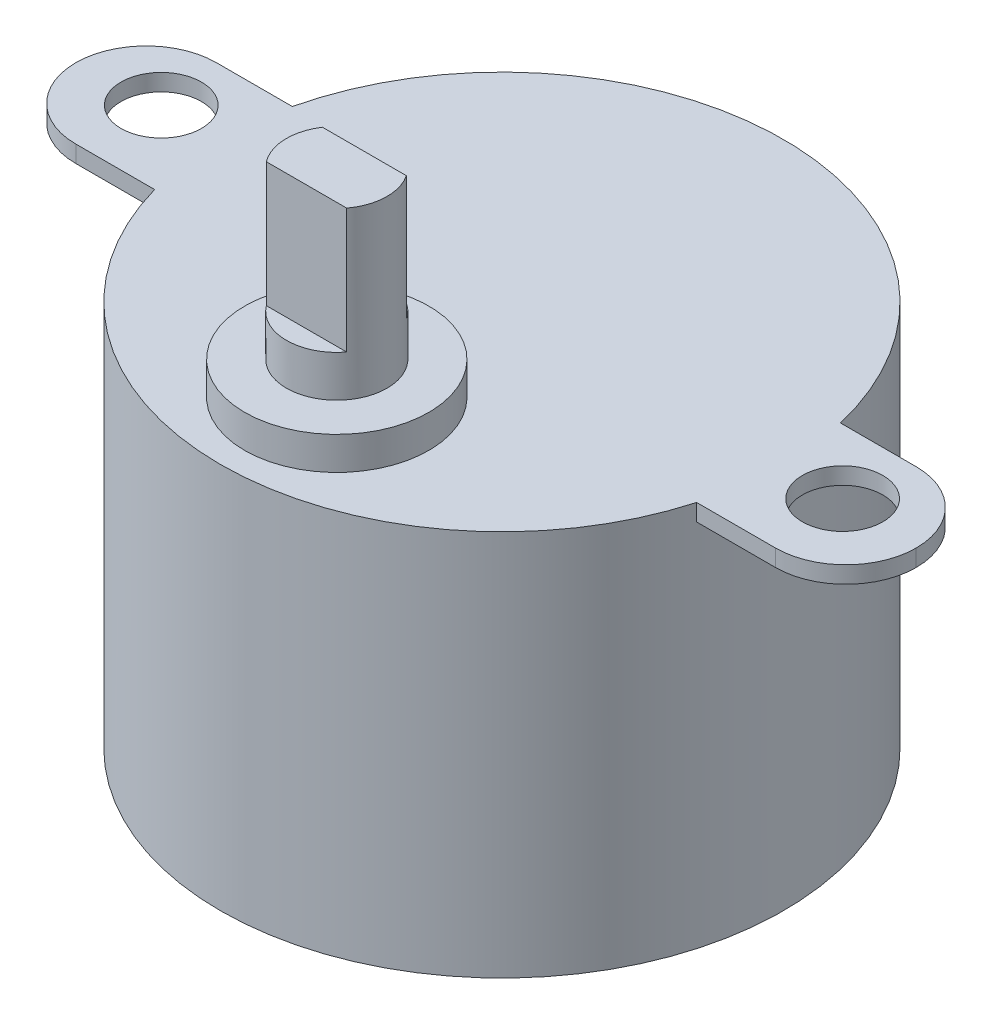
SolidWorks part; units mm, degrees
ref_plane "Front Plane" through (0, 0, 0) normal (0, 0, 1) x (1, 0, 0)
ref_plane "Top Plane" through (0, 0, 0) normal (0, 1, 0) x (1, 0, 0)
ref_plane "Right Plane" through (0, 0, 0) normal (1, 0, 0) x (0, 0, -1)
sketch "Sketch1" plane through (0, 0, 0) normal (0, 1, 0) x (1, 0, 0)
  circle A0 centre (0, 0) radius 14
extrude "Boss-Extrude1" add sketch "Sketch1" along normal blind 19.22
sketch "Sketch2" plane through (0, 19.22, 0) normal (0, 1, 0) x (1, 0, 0)
  line L0 (-20.8979, 3.2053) -> (20.8979, 3.2053)
  line L1 (-20.8979, 3.2053) -> (-20.8979, -3.7947)
  line L3 (20.8979, 3.2053) -> (20.8979, -3.7947)
  line L4 (20.8979, -3.7947) -> (-20.8979, -3.7947)
  point P4 (0, 0)
  point P7 (-20.8979, -0.2947)
  point P10 (-20.8979, 3.2053)
  dimension "D1" = 7
  dimension "D2" = 41.7958
extrude "Boss-Extrude2" add sketch "Sketch2" against normal blind 0.84
fillet "Fillet2" radius 3.5 4 edges at (20.8979, 18.8, -3.2053) (20.8979, 18.8, 3.7947) (-20.8979, 18.8, -3.2053) (-20.8979, 18.8, 3.7947)
sketch "Sketch3" plane through (0, 19.22, 0) normal (0, 1, 0) x (1, 0, 0)
  circle A1 centre (-16.9416, 0) radius 2
  circle A2 centre (16.9416, 0) radius 2
extrude "Cut-Extrude1" cut sketch "Sketch3" against normal blind 0.84
sketch "Sketch4" plane through (0, 19.22, 0) normal (0, 1, 0) x (1, 0, 0)
  circle A0 centre (0, -8.2135) radius 4.58
extrude "Boss-Extrude3" add sketch "Sketch4" along normal blind 1.64
sketch "Sketch5" plane through (0, 20.86, 0) normal (0, 1, 0) x (1, 0, 0)
  circle A0 centre (0, -8.2135) radius 2.5
extrude "Boss-Extrude4" add sketch "Sketch5" along normal blind 8.26
sketch "Sketch6" plane through (0, 29.12, 0) normal (0, 1, 0) x (1, 0, 0)
  line L1 (-3.0777, -6.8386) -> (3.0777, -6.8386)
  line L2 (3.0777, -6.8386) -> (3.0777, -9.7186)
  line L3 (3.0777, -9.7186) -> (-3.0777, -9.7186)
  line L4 (-3.0777, -9.7186) -> (-3.0777, -6.8386)
  point P4 (0, -8.2786)
  point P7 (0, -6.8386)
extrude "Cut-Extrude2" cut sketch "Sketch6" against normal blind 6.2 flip side to cut contours L2 L3 L4 L1
